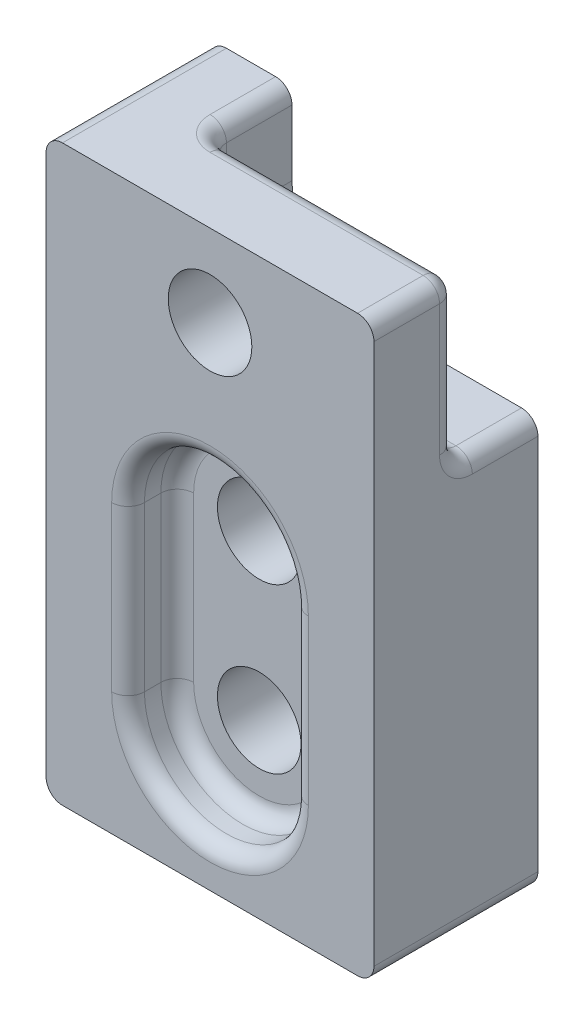
SolidWorks part; units mm, degrees
ref_plane "Front Plane" through (0, 0, 0) normal (0, 0, 1) x (1, 0, 0)
ref_plane "Top Plane" through (0, 0, 0) normal (0, 1, 0) x (1, 0, 0)
ref_plane "Right Plane" through (0, 0, 0) normal (1, 0, 0) x (0, 0, -1)
sketch "Sketch1" plane through (0, 0, 0) normal (0, 0, 1) x (1, 0, 0)
  line L0 (0, 17.5) -> (0, 7.5) construction
  line L1 (-10, -17.5) -> (10, -17.5)
  line L2 (-10, -17.5) -> (-10, 17.5)
  line L4 (10, -17.5) -> (10, 17.5)
  line L5 (0, 7.5) -> (0, 0) construction
  line L6 (-10, 17.5) -> (10, 17.5)
  line L7 (-10, 7.5) -> (10, 7.5) construction
  line L8 (0, -17.5) -> (0, -10) construction
  circle A1 centre (0, -10) radius 2.55
  circle A2 centre (0, 0) radius 2.55
  point P0 (0, 0)
extrude "Boss-Extrude1" add sketch "Sketch1" along normal blind 10
sketch "Sketch2" plane through (0, 0, 0) normal (0, 0, 1) x (1, 0, 0)
  line L0 (0, 17.5) -> (0, 12.5) construction
  line L2 (10, -17.5) -> (10, 17.5) construction
  line L4 (-5, 12.5) -> (-5, 17.5)
  line L5 (0, 7.5) -> (10, 7.5)
  line L8 (10, 17.5) -> (10, 7.5)
  line L9 (-5, 17.5) -> (10, 17.5)
  arc A1 (-5, 12.5) -> (0, 7.5) centre (0, 12.5) ccw
extrude "Cut-Extrude1" cut sketch "Sketch2" along normal blind 5
sketch "Sketch3" plane through (0, 0, 0) normal (0, 0, 1) x (1, 0, 0)
  circle A0 centre (0, 12.5) radius 2.55
extrude "Cut-Extrude2" cut sketch "Sketch3" along normal through all
sketch "Sketch4" plane through (0, 0, 0) normal (0, 0, 1) x (1, 0, 0)
  line L0 (-5, -10) -> (-5, 0)
  line L2 (5, 0) -> (5, -10)
  arc A0 (5, 0) -> (-5, 0) centre (0, 0) ccw
  arc A2 (-5, -10) -> (5, -10) centre (0, -10) ccw
extrude "Cut-Extrude4" cut sketch "Sketch4" against normal blind 3 from surface starting at face at (2.55, 12.5, 10)
fillet "Fillet1" radius 1 19 edges at (5, -5, 10) (0, -15, 10) (-5, -5, 10) (0, 5, 10) (-10, -17.5, 5) (10, -17.5, 5) (-10, 17.5, 5) (10, 17.5, 7.5) (5, 7.5, 5) (-3.5355, 8.9645, 5) (-5, 15, 5) (5, -5, 7) (0, -15, 7) (-5, -5, 7) (0, 5, 7) (10, 7.5, 2.5) (-5, 17.5, 2.5) (10, 12.5, 5) (2.5, 17.5, 5)
